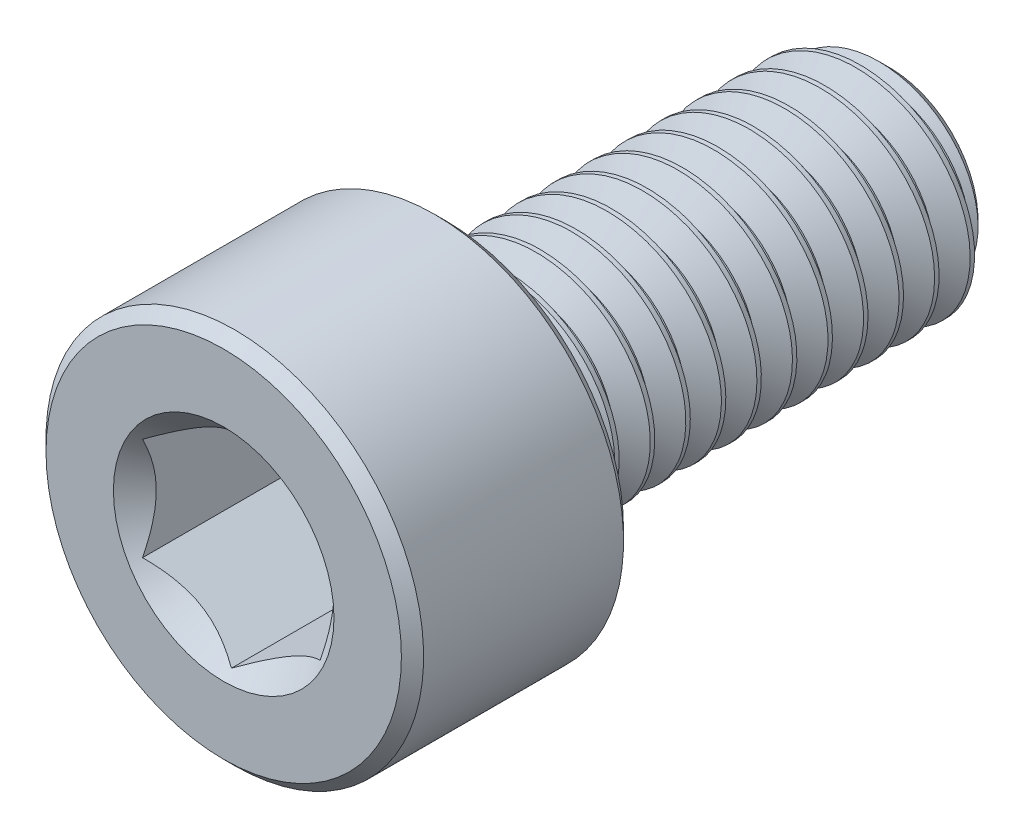
SolidWorks part; units mm, degrees
ref_plane "Front Plane" through (0, 0, 0) normal (0, 0, 1) x (1, 0, 0)
ref_plane "Top Plane" through (0, 0, 0) normal (0, 1, 0) x (1, 0, 0)
ref_plane "Right Plane" through (0, 0, 0) normal (1, 0, 0) x (0, 0, -1)
sketch "Sketch1" plane through (0, 0, 0) normal (1, 0, 0) x (0, 0, -1)
  line L0 (-7.5, 0) -> (7.5, 0) construction
  line L1 (7.5, 0) -> (7.5, 1.9804) construction
  line L2 (7.5, 1.9804) -> (6.9804, 2.5) construction
  line L3 (6.9804, 2.5) -> (6.9, 2.5) construction
  line L4 (6.9, 2.5) -> (-2.5, 2.5) construction
  line L5 (-2.5, 2.5) -> (-2.5, 4.25) construction
  line L6 (-2.5, 4.25) -> (-7.5, 4.25) construction
  line L7 (-7.5, 4.25) -> (-7.5, 0) construction
  line L8 (7.5, 1.9804) -> (7.5, 2.5) construction
  line L9 (7.45, 2.5866) -> (7.85, 1.8938) construction
  line L10 (7.85, 1.8938) -> (8.25, 2.5866) construction
  line L11 (8.25, 2.5866) -> (7.45, 2.5866) construction
  line L12 (7.85, 2.5866) -> (7.85, 2.5) construction
  line L13 (7.85, 1.8938) -> (7.85, 1.9804) construction
  line L14 (7.8, 1.9804) -> (7.9, 1.9804) construction
  line L15 (7.5, 2.5) -> (8.2, 2.5) construction
  line L16 (7.475, 2.5433) -> (8.225, 2.5433) construction
  line L17 (7.5, 0) -> (7.5, -2.5) construction
  line L18 (-2.75, 4.25) -> (-2.5, 4) construction
  line L19 (-7.25, 4.25) -> (-7.5, 4) construction
  line L20 (-2.5, 2.5) -> (-2.5, 0) construction
  line L21 (-2.5, 1.25) -> (0.8333, 1.25) construction
  line L22 (0.8333, 1.25) -> (4.1667, 1.25) construction
  line L23 (4.1667, 1.25) -> (7.5, 1.25) construction
  line L24 (0.8333, 1.25) -> (0.8333, 2.5) construction
  line L25 (0.8333, 2.5) -> (0.8333, 4.25) construction
  line L26 (4.1667, 1.25) -> (4.1667, 4.25) construction
  point P0 (-7.5, 2)
  point P3 (5.5, 2.5)
  point P4 (0, 0)
  point P18 (4.1667, 2.5)
  point P22 (7.85, 1.9804)
  point P24 (6.9, 2.5)
  point P25 (7.85, 2.5)
  point P28 (7.85, 2.5433)
  point P29 (5.5, -2.5)
  point P30 (0.8333, 2.5)
  point P31 (-5, 4.25)
  point P37 (-3.375, 4.25)
  point P38 (-7.125, 4.25)
  point P45 (0.8333, 1.25)
  point P46 (4.1667, 1.25)
  dimension "D7" = 0.25
  dimension "D8" = 0.25
  dimension "D9" = 0.25
  dimension "D10" = 0.125
  dimension "D11" = 0.625
  dimension "Drive Size" = 4
  dimension "Head Diameter" = 8.5
  dimension "Head Height" = 5
  dimension "Thread Pitch" = 0.8
  dimension "Thread Size" = 5
  dimension "Length" = 10
  dimension "D12" = 0.6
  dimension "D4" = 2
  dimension "D3" = 45
sketch "Sketch2" plane through (0, 0, 0) normal (1, 0, 0) x (0, 0, -1)
  line L0 (-7.5, 0) -> (-7.5, 4)
  line L1 (-7.25, 4.25) -> (-2.75, 4.25)
  line L2 (-2.5, 4) -> (-2.5, 2.75)
  line L4 (6.9804, 2.5) -> (7.5, 1.9804)
  line L5 (7.5, 1.9804) -> (7.5, 0)
  line L6 (-2.5, 4.25) -> (-7.5, 4.25) construction
  line L7 (7.5, 0) -> (-7.5, 0)
  line L8 (-7.25, 4.25) -> (-7.5, 4) construction
  line L10 (-7.25, 4.25) -> (-7.5, 4)
  line L14 (-2.75, 4.25) -> (-2.5, 4) construction
  line L16 (-2.75, 4.25) -> (-2.5, 4)
  line L17 (-2.5, 2.5) -> (-2.5, 4.25) construction
  line L19 (-2.25, 2.5) -> (6.9804, 2.5)
  line L20 (6.9, 2.5) -> (-2.5, 2.5) construction
  arc A1 (-2.5, 2.75) -> (-2.25, 2.5) centre (-2.25, 2.75) ccw
  dimension "D3" = 0.25
revolve "Revolve1" add sketch "Sketch2" angle 360 about L7
sketch "Sketch3" plane through (0, 0, 7.5) normal (0, 0, 1) x (1, 0, 0)
  line L1 (2, -1.1547) -> (2, 1.1547)
  line L2 (2, 1.1547) -> (0, 2.3094)
  line L3 (0, 2.3094) -> (-2, 1.1547)
  line L4 (-2, 1.1547) -> (-2, -1.1547)
  line L5 (-2, -1.1547) -> (0, -2.3094)
  line L6 (0, -2.3094) -> (2, -1.1547)
  circle A0 centre (0, 0) radius 2 construction
  circle A1 centre (0, 0) radius 4.25 construction
  circle A2 centre (0, 0) radius 4.25 construction
  circle A3 centre (0, 0) radius 2.3094 construction
  point P13 (0, 0)
  dimension "D1" = 4.6188
extrude "Cut-Extrude1" cut sketch "Sketch3" against normal offset from surface (4 mm away) 1 up to face at (0, 4, 2.5)
sketch "Sketch4" plane through (0, 0, 7.5) normal (0, 0, 1) x (1, 0, 0)
  circle A0 centre (0, 0) radius 2.4826
  dimension "D1" = 4.9652
extrude "Cut-Extrude2" cut sketch "Sketch4" against normal up to vertex (2.5 mm away) draft 45 up to point (0, 4.25, 5)
sketch "Sketch11" plane through (0, 0, 0) normal (1, 0, 0) x (0, 0, -1)
  line L0 (-7.5, 0) -> (7.5, 0) construction
  line L1 (-7.5, 0) -> (7.5, 0) construction
  line L2 (-0.625, 0) -> (-0.625, 2.5) construction
  line L3 (6.9, 2.5) -> (-2.5, 2.5) construction
  line L4 (5.625, 0) -> (5.625, 2.5) construction
  line L6 (7.5, 1.9804) -> (7.5, 2.5) construction
  point P2 (-0.625, 0)
  point P3 (5.625, 0)
  dimension "D1" = 1.875
  dimension "D2" = 1.875
sketch "Sketch6" plane through (0, 0, -7.5) normal (0, 0, -1) x (-1, 0, 0)
  circle A0 centre (0, 0) radius 2.5
curve "Helix/Spiral1" pitch 0.8 height 10.8 radius 2.5 centre (0, 0, -7.5) axis (0, 0, 1) start towards (0, 1, 0)
sketch "Sketch10" plane through (0, 0, 0) normal (1, 0, 0) x (0, 0, -1)
  line L0 (-2.25, -4.25) -> (-2.25, 4.25)
  line L5 (-7.5, 0) -> (7.5, 0) construction
  line L6 (-2.25, 2.5) -> (-2.25, -2.5) construction
  point P3 (-2.25, 0)
split "Split1" trim tools "Sketch10" bodies to split 106 resulting bodies 114 115
sketch "Sketch7" plane through (0, 0, 0) normal (1, 0, 0) x (0, 0, -1)
  line L0 (7.475, 2.5433) -> (8.225, 2.5433)
  line L1 (8.225, 2.5433) -> (7.9, 1.9804)
  line L2 (7.9, 1.9804) -> (7.8, 1.9804)
  line L3 (7.8, 1.9804) -> (7.475, 2.5433)
sweep "Cut-Sweep1" cut profiles "Sketch7" path "Helix/Spiral1" align with end faces yes
sketch "Sketch8" plane through (0, 0, 0) normal (1, 0, 0) x (0, 0, -1)
  line L0 (-2.5, 0) -> (-2.5, 2.5)
  line L1 (-2.25, -2.5) -> (-2.25, 2.5) construction
  line L2 (-2.5, 2.5) -> (-2.25, 2.5)
  line L4 (-2.25, 2.5) -> (-0.8066, 0)
  line L5 (-0.8066, 0) -> (-2.5, 0)
  line L6 (6.9, 2.5) -> (-2.5, 2.5) construction
  line L7 (-7.5, 0) -> (7.5, 0) construction
  dimension "D1" = 60
revolve "Revolve2" add sketch "Sketch8" angle 360 about L5
equation "\"D2@Sketch1\" = \"Thread Pitch@Sketch1\" / 8"
equation "\"D4@Helix/Spiral1\" = \"Thread Pitch@Sketch1\""
equation "\"D7@Sketch1\" = \"Head Height@Sketch1\" * .05"
equation "\"D8@Sketch1\"=\"D7@Sketch1\""
equation "\"D9@Sketch1\"=\"D7@Sketch1\""
equation "\"D10@Sketch1\"=\"D7@Sketch1\"/2"
equation "\"D11@Sketch1\"=\"D10@Sketch1\"*5"
equation "\"D4@Sketch1\"=\"Thread Pitch@Sketch1\"*2.5"
equation "\"D12@Sketch1\"=\"Thread Pitch@Sketch1\"*.75"
equation "\"D3@Helix/Spiral1\"=\"Length@Sketch1\"+\"Thread Pitch@Sketch1\""
equation "\"D3@Sketch2\"=\"Thread Size@Sketch1\"*0.05"
equation "\"D1@Sketch11\"=\"Length@Sketch1\"*0.1875"
equation "\"D2@Sketch11\"=\"D1@Sketch11\""
equation "\"D1@Sketch4\"=\"D1@Sketch3\"*1.075"
